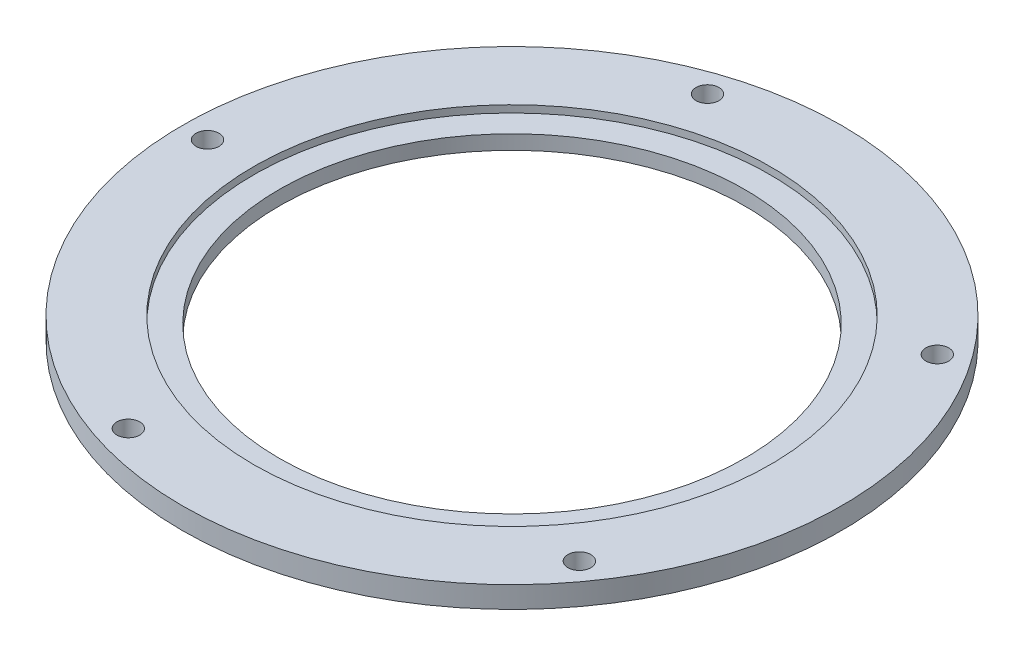
SolidWorks part; units mm, degrees
ref_plane "Front Plane" through (0, 0, 0) normal (0, 0, 1) x (1, 0, 0)
ref_plane "Top Plane" through (0, 0, 0) normal (0, 1, 0) x (1, 0, 0)
ref_plane "Right Plane" through (0, 0, 0) normal (1, 0, 0) x (0, 0, -1)
sketch "Sketch1" plane through (0, 0, 0) normal (0, 1, 0) x (1, 0, 0)
  circle A0 centre (0, 0) radius 46
  circle A1 centre (0, 0) radius 36.05
  circle A2 centre (0, 0) radius 32.5
  dimension "D1" = 92
  dimension "D2" = 72.1
  dimension "D3" = 65
extrude "Boss-Extrude1" add sketch "Sketch1" along normal blind 3 contours A0 A1 region at (-44.6989, 0, 0)
extrude "Boss-Extrude2" add sketch "Sketch1<3>" along normal blind 2 contours A1 A2 region at (-35.0304, 0, 0)
sketch "Sketch1<3>" plane through (0, 0, 0) normal (0, 1, 0) x (1, 0, 0) same geometry as "Sketch1"
hole_wizard "M3 Clearance Hole1" positions "Sketch2" profile "Sketch3" hole size "M3" standard "ANSI Metric" end condition through all
sketch "Sketch2" plane through (0, 3, 0) normal (0, 1, 0) x (1, 0, 0)
  line L1 (0, 0) -> (-42.5, 0) construction
  point P4 (-42.5, 0)
  dimension "D1" = 42.5
sketch "Sketch3" plane through (-42.5, 3, 0) normal (1, 0, 0) x (0, 0, 1)
  line L0 (0, 0) -> (0, 3)
  line L1 (0, 3) -> (1.6, 3)
  line L2 (1.6, 3) -> (1.6, 0)
  line L5 (1.6, 0) -> (0, 0)
  line L11 (0, -6.35) -> (0, 107.95) construction
  dimension "Thru Hole Dia." = 3.2
  dimension "Thru Hole Depth" = 3
pattern_circular "CirPattern1" count 5 over 360 about axis through (0, 3, 0) along (0, -1, 0) of "M3 Clearance Hole1" reverse direction yes
equation "\"Ratio\"= 15"
equation "\"Hull Diameter\"= 92"
equation "\"Fixed Ring Diameter\"= 76"
equation "\"Fixed Pin Diameter\"= 6"
equation "\"Output Ring Diameter\"= 40"
equation "\"Output Pin Diameter\"= 6"
equation "\"Disk Bearing Inner Diameter\"= 9"
equation "\"Disk Bearing Outer Diameter\"= 17"
equation "\"Disk Bearing Height\"= 5"
equation "\"Shaft Bearing Inner Diameter\"= 15"
equation "\"Shaft Bearing Outer Diameter\"= 21"
equation "\"Shaft Bearing Height\"= 4"
equation "\"Eccentricity\"= 1.5"
equation "\"Disk Height\"= 8"
equation "\"Disk Spacing\"= 5"
equation "\"Hull Height\"= 40"
equation "\"Shaft End Bearing Inner Diameter\"= 12"
equation "\"Shaft End Bearing Outer Diameter\"= 18"
equation "\"Shaft End Bearing Height\"= 4"
equation "\"Output Bearing Inner Diameter\"= 55"
equation "\"Output Bearing Outer Diameter\"= 72"
equation "\"Outer Bearing Height\"= 9"
equation "\"D1@Sketch1\"=\"Hull Diameter\""
equation "\"D2@Sketch1\"=\"Output Bearing Outer Diameter\"+0.1"
equation "\"D3@Sketch1\"=\"Output Bearing Inner Diameter\"+10"
